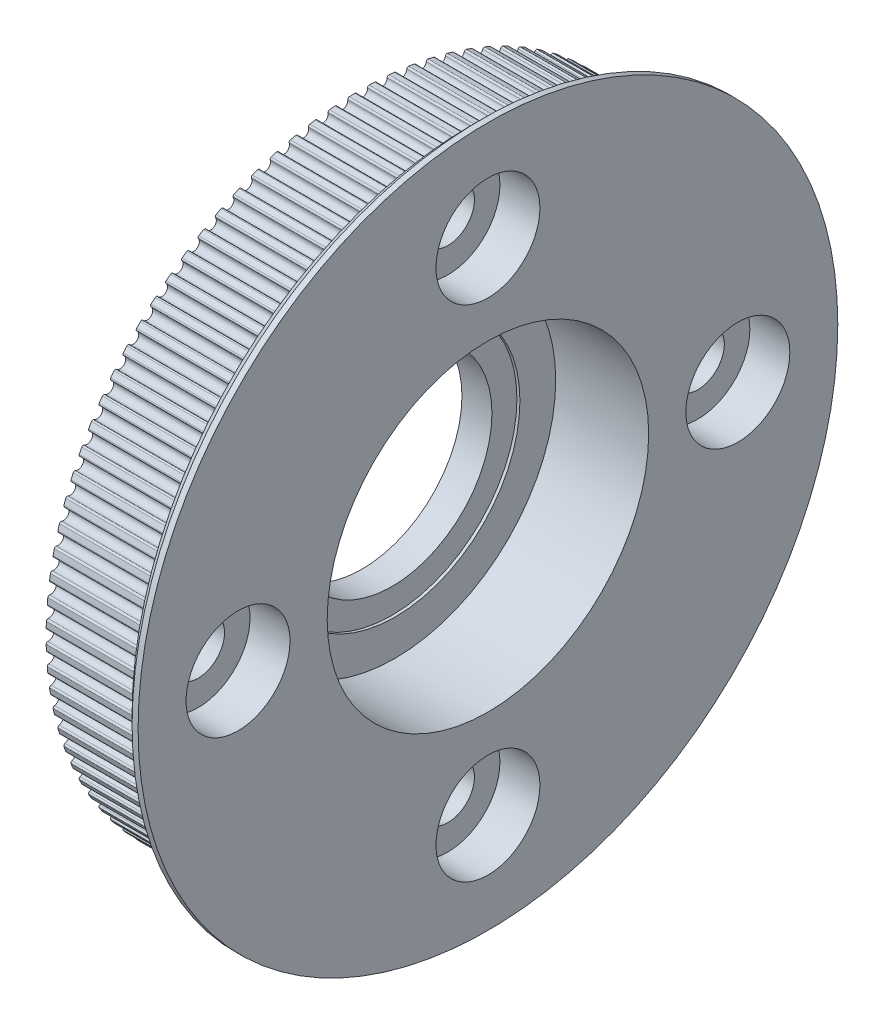
SolidWorks part; units mm, degrees
note: '?' marks a value the reader was unsure of.
ref_plane "Front Plane" through (0, 0, 0) normal (0, 0, 1) x (1, 0, 0)
ref_plane "Top Plane" through (0, 0, 0) normal (0, 1, 0) x (1, 0, 0)
ref_plane "Right Plane" through (0, 0, 0) normal (1, 0, 0) x (0, 0, -1)
sketch "Sketch1" plane through (0, 0, 0) normal (1, 0, 0) x (0, 0, -1)
  circle A0 centre (0, 0) radius 31.6
  circle A1 centre (0, 0) radius 7.65
  dimension "D1" = 63.2
  dimension "D2" = 15.3
extrude "Boss-Extrude1" add sketch "Sketch1" along normal blind 11
sketch "Sketch2" plane through (0, 0, 0) normal (1, 0, 0) x (0, 0, -1)
  circle A0 centre (0, 0) radius 31.39 construction
  circle A1 centre (0, 31.39) radius 0.55
  circle A2 centre (0, 0) radius 31.39 construction
  circle A3 centre (1.971, 31.3281) radius 0.55
  circle A4 centre (0, 0) radius 31.39 construction
  circle A5 centre (3.9342, 31.1425) radius 0.55
  circle A6 centre (0, 0) radius 31.39 construction
  circle A7 centre (5.8819, 30.834) radius 0.55
  circle A8 centre (0, 0) radius 31.39 construction
  circle A9 centre (7.8064, 30.4038) radius 0.55
  circle A10 centre (0, 0) radius 31.39 construction
  circle A11 centre (9.7, 29.8537) radius 0.55
  circle A12 centre (0, 0) radius 31.39 construction
  circle A13 centre (11.5554, 29.1857) radius 0.55
  circle A14 centre (0, 0) radius 31.39 construction
  circle A15 centre (13.3652, 28.4025) radius 0.55
  circle A16 centre (0, 0) radius 31.39 construction
  circle A17 centre (15.1222, 27.5073) radius 0.55
  circle A18 centre (0, 0) radius 31.39 construction
  circle A19 centre (16.8196, 26.5035) radius 0.55
  circle A20 centre (0, 0) radius 31.39 construction
  circle A21 centre (18.4506, 25.395) radius 0.55
  circle A22 centre (0, 0) radius 31.39 construction
  circle A23 centre (20.0087, 24.1864) radius 0.55
  circle A24 centre (0, 0) radius 31.39 construction
  circle A25 centre (21.4879, 22.8823) radius 0.55
  circle A26 centre (0, 0) radius 31.39 construction
  circle A27 centre (22.8823, 21.4879) radius 0.55
  circle A28 centre (0, 0) radius 31.39 construction
  circle A29 centre (24.1864, 20.0087) radius 0.55
  circle A30 centre (0, 0) radius 31.39 construction
  circle A31 centre (25.395, 18.4506) radius 0.55
  circle A32 centre (0, 0) radius 31.39 construction
  circle A33 centre (26.5035, 16.8196) radius 0.55
  circle A34 centre (0, 0) radius 31.39 construction
  circle A35 centre (27.5073, 15.1222) radius 0.55
  circle A36 centre (0, 0) radius 31.39 construction
  circle A37 centre (28.4025, 13.3652) radius 0.55
  circle A38 centre (0, 0) radius 31.39 construction
  circle A39 centre (29.1857, 11.5554) radius 0.55
  circle A40 centre (0, 0) radius 31.39 construction
  circle A41 centre (29.8537, 9.7) radius 0.55
  circle A42 centre (0, 0) radius 31.39 construction
  circle A43 centre (30.4038, 7.8064) radius 0.55
  circle A44 centre (0, 0) radius 31.39 construction
  circle A45 centre (30.834, 5.8819) radius 0.55
  circle A46 centre (0, 0) radius 31.39 construction
  circle A47 centre (31.1425, 3.9342) radius 0.55
  circle A48 centre (0, 0) radius 31.39 construction
  circle A49 centre (31.3281, 1.971) radius 0.55
  circle A50 centre (0, 0) radius 31.39 construction
  circle A51 centre (31.39, 0) radius 0.55
  circle A52 centre (0, 0) radius 31.39 construction
  circle A53 centre (31.3281, -1.971) radius 0.55
  circle A54 centre (0, 0) radius 31.39 construction
  circle A55 centre (31.1425, -3.9342) radius 0.55
  circle A56 centre (0, 0) radius 31.39 construction
  circle A57 centre (30.834, -5.8819) radius 0.55
  circle A58 centre (0, 0) radius 31.39 construction
  circle A59 centre (30.4038, -7.8064) radius 0.55
  circle A60 centre (0, 0) radius 31.39 construction
  circle A61 centre (29.8537, -9.7) radius 0.55
  circle A62 centre (0, 0) radius 31.39 construction
  circle A63 centre (29.1857, -11.5554) radius 0.55
  circle A64 centre (0, 0) radius 31.39 construction
  circle A65 centre (28.4025, -13.3652) radius 0.55
  circle A66 centre (0, 0) radius 31.39 construction
  circle A67 centre (27.5073, -15.1222) radius 0.55
  circle A68 centre (0, 0) radius 31.39 construction
  circle A69 centre (26.5035, -16.8196) radius 0.55
  circle A70 centre (0, 0) radius 31.39 construction
  circle A71 centre (25.395, -18.4506) radius 0.55
  circle A72 centre (0, 0) radius 31.39 construction
  circle A73 centre (24.1864, -20.0087) radius 0.55
  circle A74 centre (0, 0) radius 31.39 construction
  circle A75 centre (22.8823, -21.4879) radius 0.55
  circle A76 centre (0, 0) radius 31.39 construction
  circle A77 centre (21.4879, -22.8823) radius 0.55
  circle A78 centre (0, 0) radius 31.39 construction
  circle A79 centre (20.0087, -24.1864) radius 0.55
  circle A80 centre (0, 0) radius 31.39 construction
  circle A81 centre (18.4506, -25.395) radius 0.55
  circle A82 centre (0, 0) radius 31.39 construction
  circle A83 centre (16.8196, -26.5035) radius 0.55
  circle A84 centre (0, 0) radius 31.39 construction
  circle A85 centre (15.1222, -27.5073) radius 0.55
  circle A86 centre (0, 0) radius 31.39 construction
  circle A87 centre (13.3652, -28.4025) radius 0.55
  circle A88 centre (0, 0) radius 31.39 construction
  circle A89 centre (11.5554, -29.1857) radius 0.55
  circle A90 centre (0, 0) radius 31.39 construction
  circle A91 centre (9.7, -29.8537) radius 0.55
  circle A92 centre (0, 0) radius 31.39 construction
  circle A93 centre (7.8064, -30.4038) radius 0.55
  circle A94 centre (0, 0) radius 31.39 construction
  circle A95 centre (5.8819, -30.834) radius 0.55
  circle A96 centre (0, 0) radius 31.39 construction
  circle A97 centre (3.9342, -31.1425) radius 0.55
  circle A98 centre (0, 0) radius 31.39 construction
  circle A99 centre (1.971, -31.3281) radius 0.55
  circle A100 centre (0, 0) radius 31.39 construction
  circle A101 centre (0, -31.39) radius 0.55
  circle A102 centre (0, 0) radius 31.39 construction
  circle A103 centre (-1.971, -31.3281) radius 0.55
  circle A104 centre (0, 0) radius 31.39 construction
  circle A105 centre (-3.9342, -31.1425) radius 0.55
  circle A106 centre (0, 0) radius 31.39 construction
  circle A107 centre (-5.8819, -30.834) radius 0.55
  circle A108 centre (0, 0) radius 31.39 construction
  circle A109 centre (-7.8064, -30.4038) radius 0.55
  circle A110 centre (0, 0) radius 31.39 construction
  circle A111 centre (-9.7, -29.8537) radius 0.55
  circle A112 centre (0, 0) radius 31.39 construction
  circle A113 centre (-11.5554, -29.1857) radius 0.55
  circle A114 centre (0, 0) radius 31.39 construction
  circle A115 centre (-13.3652, -28.4025) radius 0.55
  circle A116 centre (0, 0) radius 31.39 construction
  circle A117 centre (-15.1222, -27.5073) radius 0.55
  circle A118 centre (0, 0) radius 31.39 construction
  circle A119 centre (-16.8196, -26.5035) radius 0.55
  circle A120 centre (0, 0) radius 31.39 construction
  circle A121 centre (-18.4506, -25.395) radius 0.55
  circle A122 centre (0, 0) radius 31.39 construction
  circle A123 centre (-20.0087, -24.1864) radius 0.55
  circle A124 centre (0, 0) radius 31.39 construction
  circle A125 centre (-21.4879, -22.8823) radius 0.55
  circle A126 centre (0, 0) radius 31.39 construction
  circle A127 centre (-22.8823, -21.4879) radius 0.55
  circle A128 centre (0, 0) radius 31.39 construction
  circle A129 centre (-24.1864, -20.0087) radius 0.55
  circle A130 centre (0, 0) radius 31.39 construction
  circle A131 centre (-25.395, -18.4506) radius 0.55
  circle A132 centre (0, 0) radius 31.39 construction
  circle A133 centre (-26.5035, -16.8196) radius 0.55
  circle A134 centre (0, 0) radius 31.39 construction
  circle A135 centre (-27.5073, -15.1222) radius 0.55
  circle A136 centre (0, 0) radius 31.39 construction
  circle A137 centre (-28.4025, -13.3652) radius 0.55
  circle A138 centre (0, 0) radius 31.39 construction
  circle A139 centre (-29.1857, -11.5554) radius 0.55
  circle A140 centre (0, 0) radius 31.39 construction
  circle A141 centre (-29.8537, -9.7) radius 0.55
  circle A142 centre (0, 0) radius 31.39 construction
  circle A143 centre (-30.4038, -7.8064) radius 0.55
  circle A144 centre (0, 0) radius 31.39 construction
  circle A145 centre (-30.834, -5.8819) radius 0.55
  circle A146 centre (0, 0) radius 31.39 construction
  circle A147 centre (-31.1425, -3.9342) radius 0.55
  circle A148 centre (0, 0) radius 31.39 construction
  circle A149 centre (-31.3281, -1.971) radius 0.55
  circle A150 centre (0, 0) radius 31.39 construction
  circle A151 centre (-31.39, 0) radius 0.55
  circle A152 centre (0, 0) radius 31.39 construction
  circle A153 centre (-31.3281, 1.971) radius 0.55
  circle A154 centre (0, 0) radius 31.39 construction
  circle A155 centre (-31.1425, 3.9342) radius 0.55
  circle A156 centre (0, 0) radius 31.39 construction
  circle A157 centre (-30.834, 5.8819) radius 0.55
  circle A158 centre (0, 0) radius 31.39 construction
  circle A159 centre (-30.4038, 7.8064) radius 0.55
  circle A160 centre (0, 0) radius 31.39 construction
  circle A161 centre (-29.8537, 9.7) radius 0.55
  circle A162 centre (0, 0) radius 31.39 construction
  circle A163 centre (-29.1857, 11.5554) radius 0.55
  circle A164 centre (0, 0) radius 31.39 construction
  circle A165 centre (-28.4025, 13.3652) radius 0.55
  circle A166 centre (0, 0) radius 31.39 construction
  circle A167 centre (-27.5073, 15.1222) radius 0.55
  circle A168 centre (0, 0) radius 31.39 construction
  circle A169 centre (-26.5035, 16.8196) radius 0.55
  circle A170 centre (0, 0) radius 31.39 construction
  circle A171 centre (-25.395, 18.4506) radius 0.55
  circle A172 centre (0, 0) radius 31.39 construction
  circle A173 centre (-24.1864, 20.0087) radius 0.55
  circle A174 centre (0, 0) radius 31.39 construction
  circle A175 centre (-22.8823, 21.4879) radius 0.55
  circle A176 centre (0, 0) radius 31.39 construction
  circle A177 centre (-21.4879, 22.8823) radius 0.55
  circle A178 centre (0, 0) radius 31.39 construction
  circle A179 centre (-20.0087, 24.1864) radius 0.55
  circle A180 centre (0, 0) radius 31.39 construction
  circle A181 centre (-18.4506, 25.395) radius 0.55
  circle A182 centre (0, 0) radius 31.39 construction
  circle A183 centre (-16.8196, 26.5035) radius 0.55
  circle A184 centre (0, 0) radius 31.39 construction
  circle A185 centre (-15.1222, 27.5073) radius 0.55
  circle A186 centre (0, 0) radius 31.39 construction
  circle A187 centre (-13.3652, 28.4025) radius 0.55
  circle A188 centre (0, 0) radius 31.39 construction
  circle A189 centre (-11.5554, 29.1857) radius 0.55
  circle A190 centre (0, 0) radius 31.39 construction
  circle A191 centre (-9.7, 29.8537) radius 0.55
  circle A192 centre (0, 0) radius 31.39 construction
  circle A193 centre (-7.8064, 30.4038) radius 0.55
  circle A194 centre (0, 0) radius 31.39 construction
  circle A195 centre (-5.8819, 30.834) radius 0.55
  circle A196 centre (0, 0) radius 31.39 construction
  circle A197 centre (-3.9342, 31.1425) radius 0.55
  circle A198 centre (0, 0) radius 31.39 construction
  circle A199 centre (-1.971, 31.3281) radius 0.55
  point P305 (0, 0)
  dimension "D1" = 62.78
  dimension "D2" = 1.1
  dimension "D3" = 100
extrude "Cut-Extrude1" cut sketch "Sketch2" along normal up to surface (11 mm away) up to face at (11, 0, -31.6)
fillet "Fillet1" radius 0.16 200 edges at (5.5, 31.5959, -0.51) (5.5, 31.5959, 0.51) (5.5, 31.5656, 1.4749) (5.5, 31.5015, 2.4929) (5.5, 21.2571, -23.3815) (5.5, 22.0007, -22.6833) (5.5, 22.6833, -22.0007) (5.5, 23.3815, -21.2571) (5.5, 19.747, -24.6701) (5.5, 20.5329, -24.02) (5.5, 18.159, -25.8614) (5.5, 18.9842, -25.2618) (5.5, 16.4993, -26.9506) (5.5, 17.3605, -26.404) (5.5, 14.7745, -27.9334) (5.5, 15.6684, -27.442) (5.5, 12.9914, -28.806) (5.5, 13.9143, -28.3717) (5.5, 11.157, -29.5649) (5.5, 12.1054, -29.1894) (5.5, 24.02, -20.5329) (5.5, 24.6701, -19.747) (5.5, 25.2618, -18.9842) (5.5, 25.8614, -18.159) (5.5, 26.404, -17.3605) (5.5, 26.9506, -16.4993) (5.5, 27.442, -15.6684) (5.5, 27.9334, -14.7745) (5.5, 28.3717, -13.9143) (5.5, 28.806, -12.9914) (5.5, 29.1894, -12.1054) (5.5, 29.5649, -11.157) (5.5, 29.8919, -10.2487) (5.5, 30.2071, -9.2786) (5.5, 30.4764, -8.3516) (5.5, 30.7301, -7.3636) (5.5, 30.9407, -6.4215) (5.5, 31.1318, -5.4195) (5.5, 31.2828, -4.466) (5.5, 31.4107, -3.454) (5.5, 31.5015, -2.4929) (5.5, 31.5656, -1.4749) (5.5, 31.4107, 3.454) (5.5, 31.2828, 4.466) (5.5, 31.1318, 5.4195) (5.5, 30.9407, 6.4215) (5.5, 30.7301, 7.3636) (5.5, 30.4764, 8.3516) (5.5, 30.2071, 9.2786) (5.5, 29.8919, 10.2487) (5.5, 29.5649, 11.157) (5.5, 29.1894, 12.1054) (5.5, 28.806, 12.9914) (5.5, 28.3717, 13.9143) (5.5, 27.9334, 14.7745) (5.5, 27.442, 15.6684) (5.5, 26.9506, 16.4993) (5.5, 26.404, 17.3605) (5.5, 25.8614, 18.159) (5.5, 25.2618, 18.9842) (5.5, 24.6701, 19.747) (5.5, 24.02, 20.5329) (5.5, 23.3815, 21.2571) (5.5, 22.6833, 22.0007) (5.5, 22.0007, 22.6833) (5.5, 21.2571, 23.3815) (5.5, 20.5329, 24.02) (5.5, 19.747, 24.6701) (5.5, 18.9842, 25.2618) (5.5, 18.159, 25.8614) (5.5, 17.3605, 26.404) (5.5, 16.4993, 26.9506) (5.5, 15.6684, 27.442) (5.5, 14.7745, 27.9334) (5.5, 13.9143, 28.3717) (5.5, 12.9914, 28.806) (5.5, 12.1054, 29.1894) (5.5, 11.157, 29.5649) (5.5, 10.2487, 29.8919) (5.5, 9.2786, 30.2071) (5.5, 8.3516, 30.4764) (5.5, 7.3636, 30.7301) (5.5, 6.4215, 30.9407) (5.5, 5.4195, 31.1318) (5.5, 4.466, 31.2828) (5.5, 3.454, 31.4107) (5.5, 2.4929, 31.5015) (5.5, 1.4749, 31.5656) (5.5, 0.51, 31.5959) (5.5, -0.51, 31.5959) (5.5, -1.4749, 31.5656) (5.5, -2.4929, 31.5015) (5.5, -3.454, 31.4107) (5.5, -4.466, 31.2828) (5.5, -5.4195, 31.1318) (5.5, -6.4215, 30.9407) (5.5, -7.3636, 30.7301) (5.5, -8.3516, 30.4764) (5.5, -9.2786, 30.2071) (5.5, -10.2487, 29.8919) (5.5, -11.157, 29.5649) (5.5, -12.1054, 29.1894) (5.5, -12.9914, 28.806) (5.5, -13.9143, 28.3717) (5.5, -14.7745, 27.9334) (5.5, -15.6684, 27.442) (5.5, -16.4993, 26.9506) (5.5, -17.3605, 26.404) (5.5, -18.159, 25.8614) (5.5, -18.9842, 25.2618) (5.5, -19.747, 24.6701) (5.5, -20.5329, 24.02) (5.5, -21.2571, 23.3815) (5.5, -22.0007, 22.6833) (5.5, -22.6833, 22.0007) (5.5, -23.3815, 21.2571) (5.5, -24.02, 20.5329) (5.5, -24.6701, 19.747) (5.5, -25.2618, 18.9842) (5.5, -25.8614, 18.159) (5.5, -26.404, 17.3605) (5.5, -26.9506, 16.4993) (5.5, -27.442, 15.6684) (5.5, -27.9334, 14.7745) (5.5, -28.3717, 13.9143) (5.5, -28.806, 12.9914) (5.5, -29.1894, 12.1054) (5.5, -29.5649, 11.157) (5.5, -29.8919, 10.2487) (5.5, -30.2071, 9.2786) (5.5, -30.4764, 8.3516) (5.5, -30.7301, 7.3636) (5.5, -30.9407, 6.4215) (5.5, -31.1318, 5.4195) (5.5, -31.2828, 4.466) (5.5, -31.4107, 3.454) (5.5, -31.5015, 2.4929) (5.5, -31.5656, 1.4749) (5.5, -31.5959, 0.51) (5.5, -31.5959, -0.51) (5.5, -31.5656, -1.4749) (5.5, -31.5015, -2.4929) (5.5, -31.4107, -3.454) (5.5, -31.2828, -4.466) (5.5, -31.1318, -5.4195) (5.5, -30.9407, -6.4215) (5.5, -30.7301, -7.3636) (5.5, -30.4764, -8.3516) (5.5, -30.2071, -9.2786) (5.5, -29.8919, -10.2487) (5.5, -29.5649, -11.157) (5.5, -29.1894, -12.1054) (5.5, -28.806, -12.9914) (5.5, -28.3717, -13.9143) (5.5, -27.9334, -14.7745) (5.5, -27.442, -15.6684) (5.5, -26.9506, -16.4993) (5.5, -26.404, -17.3605) (5.5, -25.8614, -18.159) (5.5, -25.2618, -18.9842) (5.5, -24.6701, -19.747) (5.5, -24.02, -20.5329) (5.5, -23.3815, -21.2571) (5.5, -22.6833, -22.0007) (5.5, -22.0007, -22.6833) (5.5, -21.2571, -23.3815) (5.5, -20.5329, -24.02) (5.5, -19.747, -24.6701) (5.5, -18.9842, -25.2618) (5.5, -18.159, -25.8614) (5.5, -17.3605, -26.404) (5.5, -16.4993, -26.9506) (5.5, -15.6684, -27.442) (5.5, -14.7745, -27.9334) (5.5, -13.9143, -28.3717) (5.5, -12.9914, -28.806) (5.5, -12.1054, -29.1894) (5.5, -11.157, -29.5649) (5.5, -10.2487, -29.8919) (5.5, -9.2786, -30.2071) (5.5, -8.3516, -30.4764) (5.5, -7.3636, -30.7301) (5.5, -6.4215, -30.9407) (5.5, -5.4195, -31.1318) (5.5, -4.466, -31.2828) (5.5, -3.454, -31.4107) (5.5, -2.4929, -31.5015) (5.5, -1.4749, -31.5656) (5.5, 9.2786, -30.2071) (5.5, 10.2487, -29.8919) (5.5, 7.3636, -30.7301) (5.5, 8.3516, -30.4764) (5.5, 5.4195, -31.1318) (5.5, 6.4215, -30.9407) (5.5, 3.454, -31.4107) (5.5, 4.466, -31.2828) (5.5, 1.4749, -31.5656) (5.5, 2.4929, -31.5015) (5.5, -0.51, -31.5959) (5.5, 0.51, -31.5959)
ref_axis "Axis1" through (11, 0, 0) along (-1, 0, 0)?
sketch "Sketch3" plane through (11, 0, 0) normal (1, 0, 0) x (0, 0, -1)
  circle A0 centre (0, 0) radius 35
  circle A1 centre (0, 0) radius 7.65
  circle A2 centre (0, 0) radius 7.65 construction
  dimension "D1" = 70
extrude "Boss-Extrude2" add sketch "Sketch3" along normal blind 1.6
sketch "Sketch6" plane through (12.6, 0, 0) normal (1, 0, 0) x (0, 0, -1)
  circle A0 centre (0, -25) radius 2.2
  circle A3 centre (-25, 0) radius 2.2
  circle A4 centre (0, 25) radius 2.2
  circle A5 centre (25, 0) radius 2.2
  point P13 (0, 0)
  dimension "D1" = 4.4
  dimension "D2" = 25
  dimension "D3" = 4
extrude "Cut-Extrude6" cut sketch "Sketch6" against normal up to surface (12.6 mm away) up to face at (0, 0, 0)
sketch "Sketch7" plane through (12.6, 0, 0) normal (1, 0, 0) x (0, 0, -1)
  circle A0 centre (0, -25) radius 3.7
  circle A1 centre (-25, 0) radius 3.7
  circle A2 centre (0, 25) radius 3.7
  circle A3 centre (25, 0) radius 3.7
  point P12 (0, 0)
  dimension "D1" = 7.4
  dimension "D2" = 4
extrude "Cut-Extrude4" cut sketch "Sketch7" against normal blind 4
chamfer "Chamfer1" distance 1 angle 45 1 edges at (11, 0, -35)
sketch "Sketch8" plane through (12.6, 0, 0) normal (1, 0, 0) x (0, 0, -1)
  circle A0 centre (0, 0) radius 15.15
  dimension "D1" = 30.3
extrude "Cut-Extrude7" cut sketch "Sketch8" against normal blind 3.3
sketch "Croquis2" plane through (12.6, 0, 0) normal (1, 0, 0) x (0, 0, -1)
  circle A0 centre (0, 0) radius 16.08
  dimension "D1" = 32.16
extrude "Cortar-Extruir2" cut sketch "Croquis2" against normal blind 9.3
sketch "Croquis6" plane through (0, 0, 0) normal (-1, 0, 0) x (0, 0, 1)
  circle A0 centre (0, 0) radius 12.5
  dimension "D1" = 25
extrude "Saliente-Extruir1" add sketch "Croquis6" against normal blind 13
sketch "Croquis7" plane through (13, 0, 0) normal (1, 0, 0) x (0, 0, -1)
  circle A0 centre (0, 0) radius 12.5
  dimension "D1" = 25
extrude "Cortar-Extruir3" cut sketch "Croquis7" against normal blind 10
sketch "Croquis8" plane through (3, 0, 0) normal (1, 0, 0) x (0, 0, -1)
  circle A0 centre (0, 0) radius 10
  dimension "D1" = 20
extrude "Cortar-Extruir4" cut sketch "Croquis8" against normal through all
sketch "Croquis9" plane through (12.6, 0, 0) normal (1, 0, 0) x (0, 0, -1)
  circle A0 centre (25, 0) radius 5.2
  circle A1 centre (0, -25) radius 5.2
  circle A2 centre (-25, 0) radius 5.2
  circle A3 centre (0, 25) radius 5.2
  dimension "D1" = 10.4
extrude "Cortar-Extruir5" cut sketch "Croquis9" against normal blind 4
sketch "Croquis10" plane through (8.6, 0, 0) normal (1, 0, 0) x (0, 0, -1)
  circle A0 centre (0, -25) radius 2.65
  dimension "D1" = 5.3
extrude "Cortar-Extruir6" cut sketch "Croquis10" against normal through all
sketch "Croquis11" plane through (8.6, 0, 0) normal (1, 0, 0) x (0, 0, -1)
  circle A0 centre (-25, 0) radius 2.65
  dimension "D1" = 5.3
extrude "Cortar-Extruir7" cut sketch "Croquis11" against normal through all
sketch "Croquis12" plane through (8.6, 0, 0) normal (1, 0, 0) x (0, 0, -1)
  circle A0 centre (0, 25) radius 2.65
  dimension "D1" = 5.3
extrude "Cortar-Extruir8" cut sketch "Croquis12" against normal through all
sketch "Croquis13" plane through (8.6, 0, 0) normal (1, 0, 0) x (0, 0, -1)
  circle A0 centre (25, 0) radius 2.65
  dimension "D1" = 5.3
extrude "Cortar-Extruir9" cut sketch "Croquis13" against normal through all
